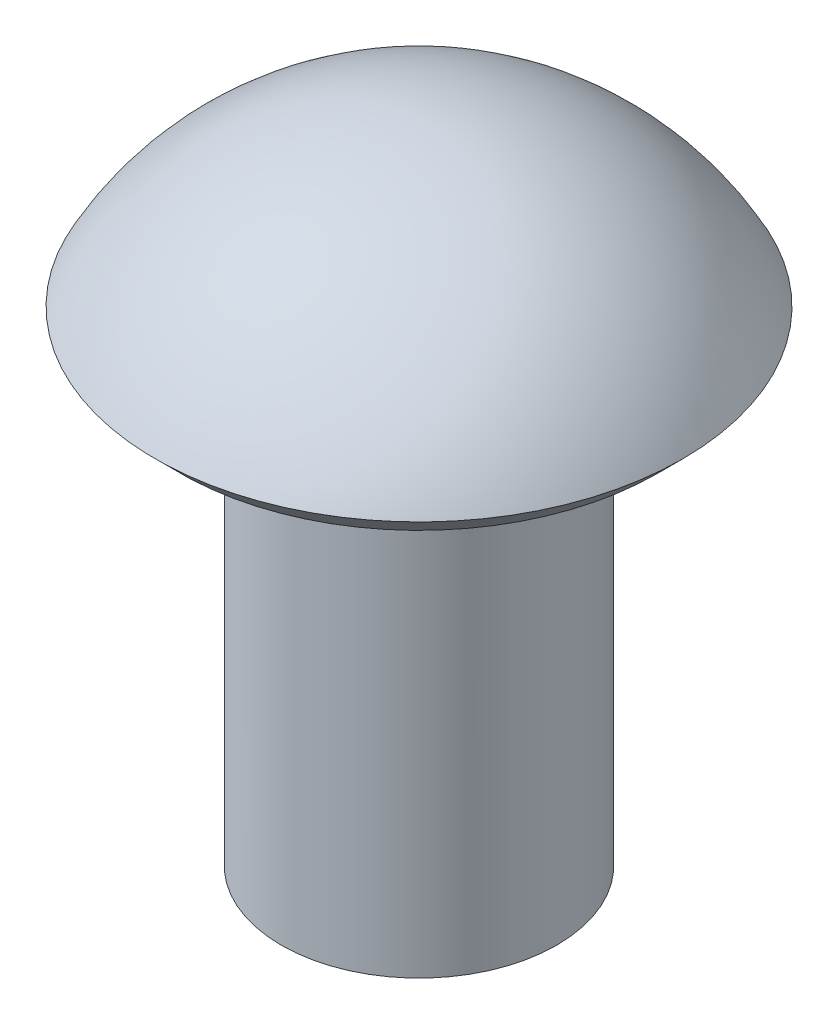
SolidWorks part; units mm, degrees
ref_plane "Front Plane" through (0, 0, 0) normal (0, 0, 1) x (1, 0, 0)
ref_plane "Top Plane" through (0, 0, 0) normal (0, 1, 0) x (1, 0, 0)
ref_plane "Right Plane" through (0, 0, 0) normal (1, 0, 0) x (0, 0, -1)
sketch "Sketch1" plane through (0, 0, 0) normal (0, 1, 0) x (1, 0, 0)
  circle A0 centre (0, 0) radius 1.5
  dimension "D1" = 3
extrude "Boss-Extrude1" add sketch "Sketch1" along normal blind 5
sketch "Sketch2" plane through (0, 5, 0) normal (0, 1, 0) x (1, 0, 0)
  circle A2 centre (0, 0) radius 4.5
  circle A3 centre (0, 0) radius 4.5
  dimension "D1" = 3
extrude "Boss-Extrude2" [suppressed] add sketch "Sketch2" along normal blind 2
fillet "Fillet1" [suppressed] radius 1
sketch "Sketch3" plane through (0, 0, 0) normal (0, 0, 1) x (1, 0, 0)
  line L3 (0, 5) -> (-3, 5)
  line L4 (1.5, 5) -> (-1.5, 5) construction
  line L5 (0, 7) -> (0, 5)
  arc A1 (-3, 5) -> (0, 7) centre (0, 3.75) cw
  point P8 (0, 0)
  point P9 (0, 0)
  dimension "D1" = 3
  dimension "D2" = 2
revolve "Revolve1" add sketch "Sketch3" angle 360 about L5
fillet "Fillet2" radius 0.5 1 edges at (0, 5, 1.5)
chamfer "Chamfer1" distance 0.4 angle 45 1 edges at (-3, 5, 0) first distance on face at (2, 5, 0)
